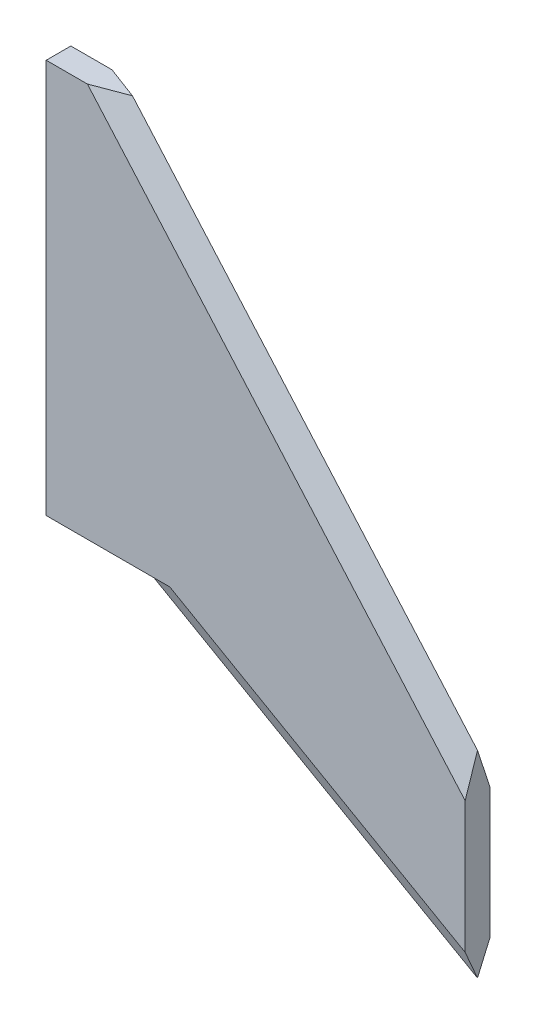
SolidWorks part; units mm, degrees
ref_plane "Front Plane" through (0, 0, 0) normal (0, 0, 1) x (1, 0, 0)
ref_plane "Top Plane" through (0, 0, 0) normal (0, 1, 0) x (1, 0, 0)
ref_plane "Right Plane" through (0, 0, 0) normal (1, 0, 0) x (0, 0, -1)
sketch "Sketch1" plane through (0, 0, 0) normal (0, 0, 1) x (1, 0, 0)
  line L0 (0, 0) -> (0, 80)
  line L1 (0, 80) -> (70, 0)
  line L2 (70, 0) -> (70, -40)
  line L3 (70, -40) -> (0, 0)
  dimension "D1" = 80
  dimension "D2" = 70
  dimension "D3" = 80
  dimension "D4" = 40
extrude "Boss-Extrude1" add sketch "Sketch1" along normal mid plane 5
sketch "Sketch7" plane through (0, 0, 0) normal (-1, 0, 0) x (0, 0, 1)
  line L4 (-2.5, 80) -> (-2.5, 0)
  line L5 (-2.5, 0) -> (2.5, 0)
  line L6 (2.5, 0) -> (2.5, 80)
  line L7 (2.5, 80) -> (-2.5, 80)
  line L8 (-2.5, 80) -> (-2.5, 0)
  line L9 (-2.5, 0) -> (2.5, 0)
  line L10 (2.5, 0) -> (2.5, 80)
  line L11 (2.5, 80) -> (-2.5, 80)
  dimension "D1" = 0
extrude "Boss-Extrude2" add sketch "Sketch7" along normal blind 25
chamfer "Chamfer1" distance 2.5 distance2 5 2 edges at (35, -20, 2.5) (35, 40, 2.5) first distance on face at (35, -20, 0) first distance on face at (35, 40, 0)
chamfer "Chamfer2" distance 5 distance2 2.5 2 edges at (35, -20, -2.5) (35, 40, -2.5) first distance on face at (15, 20, -2.5)
sketch "Sketch8" plane through (-25, 0, 0) normal (-1, 0, 0) x (0, 0, 1)
  line L4 (2.5, 80) -> (-2.5, 80)
  line L5 (-2.5, 80) -> (-2.5, 0)
  line L6 (-2.5, 0) -> (2.5, 0)
  line L7 (2.5, 0) -> (2.5, 80)
  line L8 (2.5, 80) -> (-2.5, 80)
  line L9 (-2.5, 80) -> (-2.5, 0)
  line L10 (-2.5, 0) -> (2.5, 0)
  line L11 (2.5, 0) -> (2.5, 80)
  dimension "D1" = 0
extrude "Cut-Extrude1" cut sketch "Sketch8" against normal blind 10
